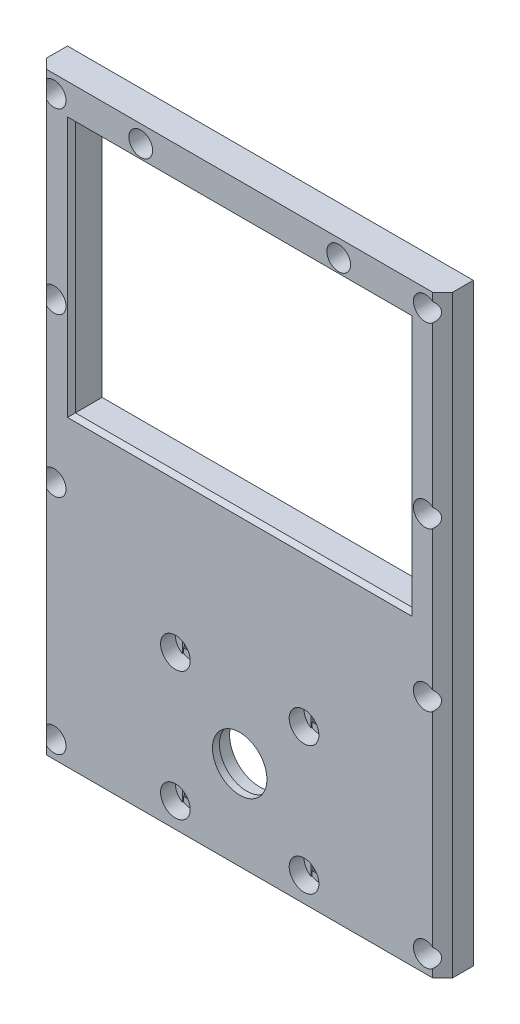
SolidWorks part; units mm, degrees
ref_plane "Front Plane" through (0, 0, 0) normal (0, 0, 1) x (1, 0, 0)
ref_plane "Top Plane" through (0, 0, 0) normal (0, 1, 0) x (1, 0, 0)
ref_plane "Right Plane" through (0, 0, 0) normal (1, 0, 0) x (0, 0, -1)
sketch "Sketch1" plane through (0, 0, 0) normal (0, 0, 1) x (1, 0, 0)
  line L1 (-41, -60) -> (41, -60)
  line L2 (-41, -60) -> (-41, 60)
  line L3 (-41, 60) -> (41, 60)
  line L4 (41, -60) -> (41, 60)
  line L5 (-41, -60) -> (41, 60) construction
  line L6 (-41, 60) -> (41, -60) construction
  line L7 (-34, -53) -> (34, -53)
  line L8 (-34, -53) -> (-34, 53)
  line L9 (-34, 53) -> (34, 53)
  line L10 (34, -53) -> (34, 53)
  line L11 (-34, -53) -> (34, 53) construction
  line L12 (-34, 53) -> (34, -53) construction
  point P0 (0, 0)
  point P6 (0, 0)
  dimension "D1" = 120
  dimension "D2" = 82
  dimension "D3" = 7
  dimension "D4" = 7
extrude "Boss-Extrude1" add sketch "Sketch1" along normal blind 7
sketch "Sketch2" plane through (0, 0, 7) normal (0, 0, 1) x (1, 0, 0)
  line L0 (34, -53) -> (34, 53) construction
  line L1 (-34, -53) -> (34, -53)
  line L2 (-34, -53) -> (-34, -17)
  line L3 (-34, -17) -> (34, -17)
  line L4 (34, -53) -> (34, -17)
  dimension "D1" = 36
extrude "Boss-Extrude2" add sketch "Sketch2" against normal up to surface (7 mm away) up to face at (0, 0, 0)
sketch "Sketch3" plane through (0, 0, 0) normal (0, 0, -1) x (-1, 0, 0)
  line L0 (0, -60) -> (0, -42) construction
  line L1 (41, -60) -> (-41, -60) construction
  circle A0 centre (0, -42) radius 5.5
  dimension "D1" = 11
  dimension "D2" = 18
extrude "Cut-Extrude1" cut sketch "Sketch3" against normal through all
sketch "Sketch4" plane through (0, 0, 0) normal (0, 0, -1) x (-1, 0, 0)
  circle A0 centre (0, -42) radius 6.05
  dimension "D1" = 12.1
extrude "Cut-Extrude2" cut sketch "Sketch4" against normal offset from surface (5.6 mm away) 1.4 up to face at (-5.5, -42, 7)
sketch "Sketch5" plane through (0, 0, 0) normal (0, 0, -1) x (-1, 0, 0)
  circle A0 centre (0, -42) radius 11
  dimension "D1" = 22
extrude "Cut-Extrude3" cut sketch "Sketch5" against normal offset from surface (3 mm away) 2.6 up to face at (-6.05, -42, 5.6)
sketch "Sketch6" plane through (0, 0, 0) normal (0, 0, -1) x (-1, 0, 0)
  line L1 (-13, -55) -> (13, -55) construction
  line L2 (-13, -55) -> (-13, -29) construction
  line L3 (-13, -29) -> (13, -29) construction
  line L4 (13, -55) -> (13, -29) construction
  line L5 (-13, -55) -> (13, -29) construction
  line L6 (-13, -29) -> (13, -55) construction
  circle A0 centre (-13, -29) radius 1.6
  circle A1 centre (13, -29) radius 1.6
  circle A2 centre (13, -55) radius 1.6
  circle A3 centre (-13, -55) radius 1.6
  point P0 (0, -42)
  dimension "D2" = 3.2
  dimension "D1" = 26
extrude "Cut-Extrude4" cut sketch "Sketch6" against normal through all
sketch "Sketch7" plane through (0, 0, 0) normal (0, 0, -1) x (-1, 0, 0)
  line L1 (-25, -61) -> (25, -61)
  line L2 (-25, -61) -> (-25, -23)
  line L3 (-25, -23) -> (25, -23)
  line L4 (25, -61) -> (25, -23)
  line L5 (-25, -61) -> (25, -23) construction
  line L6 (-25, -23) -> (25, -61) construction
  point P0 (0, -42)
  dimension "D1" = 50
  dimension "D2" = 38
extrude "Cut-Extrude5" cut sketch "Sketch7" against normal blind 1
sketch "Sketch8" plane through (0, 0, 7) normal (0, 0, 1) x (1, 0, 0)
  circle A0 centre (-13, -29) radius 3
  circle A1 centre (13, -29) radius 3
  circle A2 centre (13, -55) radius 3
  circle A3 centre (-13, -55) radius 3
  dimension "D1" = 6
extrude "Cut-Extrude6" cut sketch "Sketch8" against normal blind 3
sketch "Sketch9" plane through (0, 0, 7) normal (0, 0, 1) x (1, 0, 0)
  line L0 (-41, 60) -> (-41, -60) construction
  line L1 (-37.5, -56.5) -> (37.5, -56.5) construction
  line L2 (-37.5, -56.5) -> (-37.5, 56.5) construction
  line L3 (-37.5, 56.5) -> (37.5, 56.5) construction
  line L4 (37.5, -56.5) -> (37.5, 56.5) construction
  line L5 (-37.5, -56.5) -> (37.5, 56.5) construction
  line L6 (-37.5, 56.5) -> (37.5, -56.5) construction
  line L7 (41, 60) -> (-41, 60) construction
  circle A0 centre (-37.5, 56.5) radius 1.35
  circle A1 centre (37.5, 56.5) radius 1.35
  circle A4 centre (-37.5, -56.5) radius 1.35
  circle A5 centre (37.5, -56.5) radius 1.35
  circle A6 centre (-37.5, 20.5) radius 1.35
  circle A7 centre (37.5, 20.5) radius 1.35
  circle A8 centre (37.5, -11.5) radius 1.35
  circle A9 centre (-37.5, -11.5) radius 1.35
  point P0 (0, 0)
  dimension "D3" = 2.7
  dimension "D1" = 3.5
  dimension "D2" = 3.5
  dimension "D4" = 45
  dimension "D5" = 36
extrude "Cut-Extrude7" cut sketch "Sketch9" against normal through all
sketch "Sketch10" plane through (0, 0, 7) normal (0, 0, 1) x (1, 0, 0)
  circle A0 centre (-37.5, 56.5) radius 2.4
  circle A1 centre (37.5, 20.5) radius 2.4
  circle A2 centre (-37.5, 20.5) radius 2.4
  circle A3 centre (37.5, 56.5) radius 2.4
  circle A4 centre (-37.5, -56.5) radius 2.4
  circle A5 centre (37.5, -56.5) radius 2.4
  circle A6 centre (-37.5, -11.5) radius 2.4
  circle A7 centre (37.5, -11.5) radius 2.4
  dimension "D1" = 4.8
extrude "Cut-Extrude8" cut sketch "Sketch10" against normal blind 5
chamfer "Chamfer1" distance 2 angle 45 2 edges at (-41, 0, 7) (41, 0, 7)
sketch "Sketch11" plane through (0, 0, 7) normal (0, 0, 1) x (1, 0, 0)
  line L0 (34, -17) -> (34, 53) construction
  line L1 (-34, -17) -> (34, -17)
  line L2 (-34, -17) -> (-34, 2)
  line L3 (-34, 2) -> (34, 2)
  line L4 (34, -17) -> (34, 2)
  line L5 (-39, -60) -> (39, -60) construction
  dimension "D1" = 62
extrude "Boss-Extrude3" add sketch "Sketch11" against normal up to surface (7 mm away) up to face at (-36.15, -56.5, 0)
sketch "Sketch12" plane through (0, 0, 7) normal (0, 0, 1) x (1, 0, 0)
  line L0 (-37.5, 56.5) -> (37.5, 56.5) construction
  line L1 (-20, 56.5) -> (20, 56.5) construction
  circle A0 centre (-20, 56.5) radius 1.35
  circle A1 centre (20, 56.5) radius 1.35
  circle A2 centre (-37.5, 56.5) radius 1.35 construction
  point P7 (0, 56.5)
  dimension "D1" = 40
extrude "Cut-Extrude9" cut sketch "Sketch12" against normal through all
sketch "Sketch13" plane through (0, 0, 7) normal (0, 0, 1) x (1, 0, 0)
  circle A0 centre (-20, 56.5) radius 2.4
  circle A1 centre (20, 56.5) radius 2.4
  circle A2 centre (-37.5, 56.5) radius 2.4 construction
extrude "Cut-Extrude10" cut sketch "Sketch13" against normal up to surface (5 mm away) up to face at (-35.1, 56.5, 2)
chamfer "Chamfer2" distance 0.8 angle 45 11 edges at (0, 53, 0) (-34, 27.5, 0) (0, 53, 7) (-34, 27.5, 7) (34, 27.5, 7) (34, 27.5, 0) (0, 2, 7) (0, 2, 0) (-41, 0, 0) (0, 60, 0) (41, 0, 0)
sketch "Sketch14" plane through (0, 0, 2) normal (0, 0, 1) x (1, 0, 0)
  line L2 (-38.85, -13.4843) -> (-38.85, -9.5157)
  line L4 (-36.15, -13.4843) -> (-36.15, -9.5157)
  line L5 (-38.85, -13.4843) -> (-36.15, -9.5157) construction
  line L6 (-38.85, -9.5157) -> (-36.15, -13.4843) construction
  line L14 (-38.85, -58.4843) -> (-38.85, -54.5157)
  line L16 (-36.15, -58.4843) -> (-36.15, -54.5157)
  line L17 (-38.85, -58.4843) -> (-36.15, -54.5157) construction
  line L18 (-38.85, -54.5157) -> (-36.15, -58.4843) construction
  line L26 (-38.85, 18.5157) -> (-38.85, 22.4843)
  line L28 (-36.15, 18.5157) -> (-36.15, 22.4843)
  line L29 (-38.85, 18.5157) -> (-36.15, 22.4843) construction
  line L30 (-38.85, 22.4843) -> (-36.15, 18.5157) construction
  line L32 (-21.35, 54.5157) -> (-21.35, 58.4843)
  line L34 (-18.65, 54.5157) -> (-18.65, 58.4843)
  line L35 (-21.35, 54.5157) -> (-18.65, 58.4843) construction
  line L36 (-21.35, 58.4843) -> (-18.65, 54.5157) construction
  line L38 (-38.85, 54.5157) -> (-38.85, 58.4843)
  line L40 (-36.15, 54.5157) -> (-36.15, 58.4843)
  line L41 (-38.85, 54.5157) -> (-36.15, 58.4843) construction
  line L42 (-38.85, 58.4843) -> (-36.15, 54.5157) construction
  arc A0 (-39, -13.3735) -> (-39, -9.6265) centre (-37.5, -11.5) ccw construction
  circle A2 centre (-37.5, -56.5) radius 2.4 construction
  circle A4 centre (-37.5, 20.5) radius 2.4 construction
  circle A5 centre (-20, 56.5) radius 2.4 construction
  circle A6 centre (-37.5, 56.5) radius 2.4 construction
  circle A7 centre (-37.5, 56.5) radius 1.35 construction
  circle A8 centre (-20, 56.5) radius 1.35 construction
  circle A9 centre (-37.5, 20.5) radius 1.35 construction
  circle A10 centre (-37.5, -11.5) radius 1.35 construction
  circle A12 centre (-37.5, -56.5) radius 1.35 construction
  arc A16 (-21.35, 54.5157) -> (-18.65, 54.5157) centre (-20, 56.5) ccw
  arc A17 (-36.15, 58.4843) -> (-38.85, 58.4843) centre (-37.5, 56.5) ccw
  arc A18 (-36.15, 22.4843) -> (-38.85, 22.4843) centre (-37.5, 20.5) ccw
  arc A20 (-38.85, -13.4843) -> (-36.15, -13.4843) centre (-37.5, -11.5) ccw
  arc A22 (-36.15, -54.5157) -> (-38.85, -54.5157) centre (-37.5, -56.5) ccw
  arc A23 (-38.85, 54.5157) -> (-36.15, 54.5157) centre (-37.5, 56.5) ccw
  arc A24 (-18.65, 58.4843) -> (-21.35, 58.4843) centre (-20, 56.5) ccw
  arc A25 (-38.85, 18.5157) -> (-36.15, 18.5157) centre (-37.5, 20.5) ccw
  arc A26 (-36.15, -9.5157) -> (-38.85, -9.5157) centre (-37.5, -11.5) ccw
  arc A29 (-38.85, -58.4843) -> (-36.15, -58.4843) centre (-37.5, -56.5) ccw
  point P0 (-37.5, -11.5)
  point P17 (-37.5, -56.5)
  point P33 (-37.5, 20.5)
  point P41 (-20, 56.5)
  point P49 (-37.5, 56.5)
extrude "Cut-Extrude11" cut sketch "Sketch14" against normal blind 0.2
sketch "Sketch15" plane through (0, 0, 1.8) normal (0, 0, 1) x (1, 0, 0)
  line L0 (-36.15, -56.5) -> (-36.15, -54.5157) construction
  line L1 (-38.85, -57.85) -> (-36.15, -57.85)
  line L2 (-38.85, -57.85) -> (-38.85, -55.15)
  line L3 (-38.85, -55.15) -> (-36.15, -55.15)
  line L4 (-36.15, -57.85) -> (-36.15, -55.15)
  line L5 (-38.85, -57.85) -> (-36.15, -55.15) construction
  line L6 (-38.85, -55.15) -> (-36.15, -57.85) construction
  line L7 (-36.15, 20.5) -> (-36.15, 22.4843) construction
  line L8 (-38.85, -12.85) -> (-36.15, -12.85)
  line L9 (-38.85, -12.85) -> (-38.85, -10.15)
  line L10 (-38.85, -10.15) -> (-36.15, -10.15)
  line L11 (-36.15, -12.85) -> (-36.15, -10.15)
  line L12 (-38.85, -12.85) -> (-36.15, -10.15) construction
  line L13 (-38.85, -10.15) -> (-36.15, -12.85) construction
  line L14 (-38.85, 19.15) -> (-36.15, 19.15)
  line L15 (-38.85, 19.15) -> (-38.85, 21.85)
  line L16 (-38.85, 21.85) -> (-36.15, 21.85)
  line L17 (-36.15, 19.15) -> (-36.15, 21.85)
  line L18 (-38.85, 19.15) -> (-36.15, 21.85) construction
  line L19 (-38.85, 21.85) -> (-36.15, 19.15) construction
  line L20 (-36.15, 54.5157) -> (-36.15, 58.4843) construction
  line L21 (-38.85, 55.15) -> (-36.15, 55.15)
  line L22 (-38.85, 55.15) -> (-38.85, 57.85)
  line L23 (-38.85, 57.85) -> (-36.15, 57.85)
  line L24 (-36.15, 55.15) -> (-36.15, 57.85)
  line L25 (-38.85, 55.15) -> (-36.15, 57.85) construction
  line L26 (-38.85, 57.85) -> (-36.15, 55.15) construction
  line L27 (-18.65, 54.5157) -> (-18.65, 58.4843) construction
  line L28 (-21.35, 55.15) -> (-18.65, 55.15)
  line L29 (-21.35, 55.15) -> (-21.35, 57.85)
  line L30 (-21.35, 57.85) -> (-18.65, 57.85)
  line L31 (-18.65, 55.15) -> (-18.65, 57.85)
  line L32 (-21.35, 55.15) -> (-18.65, 57.85) construction
  line L33 (-21.35, 57.85) -> (-18.65, 55.15) construction
  arc A0 (-36.15, -11.5) -> (-38.85, -11.5) centre (-37.5, -11.5) ccw construction
  arc A1 (-36.15, 20.5) -> (-38.85, 20.5) centre (-37.5, 20.5) ccw construction
  arc A2 (-18.65, 56.5) -> (-21.35, 56.5) centre (-20, 56.5) ccw construction
  arc A3 (-36.15, 56.5) -> (-38.85, 56.5) centre (-37.5, 56.5) ccw construction
  point P0 (-37.5, -56.5)
  point P8 (-37.5, -11.5)
  point P17 (-37.5, 20.5)
  point P28 (-37.5, 56.5)
  point P36 (-20, 56.5)
extrude "Cut-Extrude12" cut sketch "Sketch15" against normal blind 0.2
sketch "Sketch16" plane through (0, 0, 4) normal (0, 0, 1) x (1, 0, 0)
  line L2 (-14.6, -31.5377) -> (-14.6, -26.4623)
  line L4 (-11.4, -31.5377) -> (-11.4, -26.4623)
  line L5 (-14.6, -31.5377) -> (-11.4, -26.4623) construction
  line L6 (-14.6, -26.4623) -> (-11.4, -31.5377) construction
  line L8 (-14.6, -57.5377) -> (-14.6, -52.4623)
  line L10 (-11.4, -57.5377) -> (-11.4, -52.4623)
  line L11 (-14.6, -57.5377) -> (-11.4, -52.4623) construction
  line L12 (-14.6, -52.4623) -> (-11.4, -57.5377) construction
  circle A0 centre (-13, -29) radius 3 construction
  circle A1 centre (-13, -55) radius 3 construction
  circle A2 centre (-13, -55) radius 1.6 construction
  circle A3 centre (-13, -29) radius 1.6 construction
  circle A4 centre (-13, -55) radius 3 construction
  circle A5 centre (-13, -29) radius 3 construction
  arc A6 (-11.4, -52.4623) -> (-14.6, -52.4623) centre (-13, -55) ccw
  arc A7 (-14.6, -31.5377) -> (-11.4, -31.5377) centre (-13, -29) ccw
  arc A8 (-11.4, -26.4623) -> (-14.6, -26.4623) centre (-13, -29) ccw
  arc A9 (-14.6, -57.5377) -> (-11.4, -57.5377) centre (-13, -55) ccw
  point P0 (-13, -29)
  point P8 (-13, -55)
extrude "Cut-Extrude13" cut sketch "Sketch16" against normal blind 0.2
sketch "Sketch17" plane through (0, 0, 3.8) normal (0, 0, 1) x (1, 0, 0)
  line L0 (-11.4, -31.5377) -> (-11.4, -26.4623) construction
  line L1 (-14.6, -30.6) -> (-11.4, -30.6)
  line L2 (-14.6, -30.6) -> (-14.6, -27.4)
  line L3 (-14.6, -27.4) -> (-11.4, -27.4)
  line L4 (-11.4, -30.6) -> (-11.4, -27.4)
  line L5 (-14.6, -30.6) -> (-11.4, -27.4) construction
  line L6 (-14.6, -27.4) -> (-11.4, -30.6) construction
  line L7 (-11.4, -57.5377) -> (-11.4, -52.4623) construction
  line L8 (-14.6, -56.6) -> (-11.4, -56.6)
  line L9 (-14.6, -56.6) -> (-14.6, -53.4)
  line L10 (-14.6, -53.4) -> (-11.4, -53.4)
  line L11 (-11.4, -56.6) -> (-11.4, -53.4)
  line L12 (-14.6, -56.6) -> (-11.4, -53.4) construction
  line L13 (-14.6, -53.4) -> (-11.4, -56.6) construction
  arc A0 (-11.4, -55) -> (-14.6, -55) centre (-13, -55) ccw construction
  arc A1 (-11.4, -29) -> (-14.6, -29) centre (-13, -29) ccw construction
  point P0 (-13, -29)
  point P8 (-13, -55)
extrude "Cut-Extrude14" cut sketch "Sketch17" against normal blind 0.2
mirror "Mirror1" about plane through (0, 0, 0) normal (1, 0, 0) of "Cut-Extrude11", "Cut-Extrude12", "Cut-Extrude13", "Cut-Extrude14"
